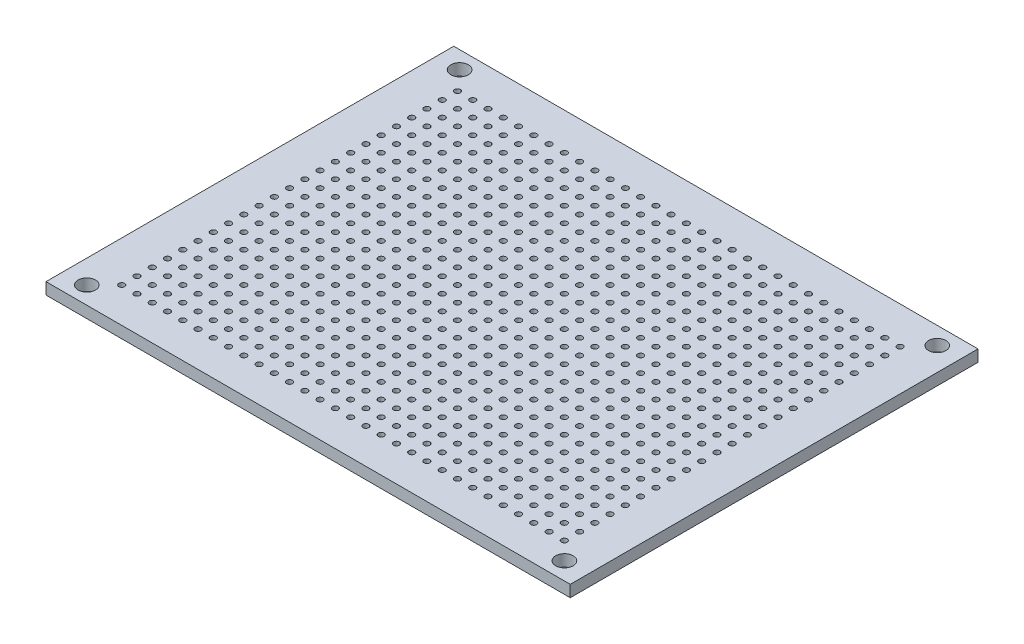
SolidWorks part; units mm, degrees
ref_plane "Front Plane" through (0, 0, 0) normal (0, 0, 1) x (1, 0, 0)
ref_plane "Top Plane" through (0, 0, 0) normal (0, 1, 0) x (1, 0, 0)
ref_plane "Right Plane" through (0, 0, 0) normal (1, 0, 0) x (0, 0, -1)
sketch "Sketch1" plane through (0, 0, 0) normal (0, 1, 0) x (1, 0, 0)
  line L0 (0, -44.7135) -> (0, 42.4067) construction
  line L1 (-45, 35) -> (45, 35)
  line L2 (-45, 35) -> (-45, -35)
  line L3 (-45, -35) -> (45, -35)
  line L4 (45, 35) -> (45, -35)
  line L5 (-45, 35) -> (45, -35) construction
  line L6 (-45, -35) -> (45, 35) construction
  line L7 (-54.5641, 0) -> (59.3866, 0) construction
  circle A0 centre (-41, -32) radius 1.5
  circle A1 centre (-38, -29) radius 0.5
  circle A2 centre (-35.38, -29) radius 0.5
  circle A3 centre (-32.76, -29) radius 0.5
  circle A4 centre (-30.14, -29) radius 0.5
  circle A5 centre (-27.52, -29) radius 0.5
  circle A6 centre (-24.9, -29) radius 0.5
  circle A7 centre (-22.28, -29) radius 0.5
  circle A8 centre (-19.66, -29) radius 0.5
  circle A9 centre (-17.04, -29) radius 0.5
  circle A10 centre (-14.42, -29) radius 0.5
  circle A11 centre (-11.8, -29) radius 0.5
  circle A12 centre (-9.18, -29) radius 0.5
  circle A13 centre (-6.56, -29) radius 0.5
  circle A14 centre (-3.94, -29) radius 0.5
  circle A15 centre (-1.32, -29) radius 0.5
  circle A16 centre (1.3, -29) radius 0.5
  circle A17 centre (3.92, -29) radius 0.5
  circle A18 centre (6.54, -29) radius 0.5
  circle A19 centre (9.16, -29) radius 0.5
  circle A20 centre (11.78, -29) radius 0.5
  circle A21 centre (14.4, -29) radius 0.5
  circle A22 centre (17.02, -29) radius 0.5
  circle A23 centre (19.64, -29) radius 0.5
  circle A24 centre (22.26, -29) radius 0.5
  circle A25 centre (24.88, -29) radius 0.5
  circle A26 centre (27.5, -29) radius 0.5
  circle A27 centre (30.12, -29) radius 0.5
  circle A28 centre (32.74, -29) radius 0.5
  circle A29 centre (35.36, -29) radius 0.5
  circle A30 centre (37.98, -29) radius 0.5
  circle A31 centre (-38, -26.38) radius 0.5
  circle A32 centre (-35.38, -26.38) radius 0.5
  circle A33 centre (-32.76, -26.38) radius 0.5
  circle A34 centre (-30.14, -26.38) radius 0.5
  circle A35 centre (-27.52, -26.38) radius 0.5
  circle A36 centre (-24.9, -26.38) radius 0.5
  circle A37 centre (-22.28, -26.38) radius 0.5
  circle A38 centre (-19.66, -26.38) radius 0.5
  circle A39 centre (-17.04, -26.38) radius 0.5
  circle A40 centre (-14.42, -26.38) radius 0.5
  circle A41 centre (-11.8, -26.38) radius 0.5
  circle A42 centre (-9.18, -26.38) radius 0.5
  circle A43 centre (-6.56, -26.38) radius 0.5
  circle A44 centre (-3.94, -26.38) radius 0.5
  circle A45 centre (-1.32, -26.38) radius 0.5
  circle A46 centre (1.3, -26.38) radius 0.5
  circle A47 centre (3.92, -26.38) radius 0.5
  circle A48 centre (6.54, -26.38) radius 0.5
  circle A49 centre (9.16, -26.38) radius 0.5
  circle A50 centre (11.78, -26.38) radius 0.5
  circle A51 centre (14.4, -26.38) radius 0.5
  circle A52 centre (17.02, -26.38) radius 0.5
  circle A53 centre (19.64, -26.38) radius 0.5
  circle A54 centre (22.26, -26.38) radius 0.5
  circle A55 centre (24.88, -26.38) radius 0.5
  circle A56 centre (27.5, -26.38) radius 0.5
  circle A57 centre (30.12, -26.38) radius 0.5
  circle A58 centre (32.74, -26.38) radius 0.5
  circle A59 centre (35.36, -26.38) radius 0.5
  circle A60 centre (37.98, -26.38) radius 0.5
  circle A61 centre (-38, -23.76) radius 0.5
  circle A62 centre (-35.38, -23.76) radius 0.5
  circle A63 centre (-32.76, -23.76) radius 0.5
  circle A64 centre (-30.14, -23.76) radius 0.5
  circle A65 centre (-27.52, -23.76) radius 0.5
  circle A66 centre (-24.9, -23.76) radius 0.5
  circle A67 centre (-22.28, -23.76) radius 0.5
  circle A68 centre (-19.66, -23.76) radius 0.5
  circle A69 centre (-17.04, -23.76) radius 0.5
  circle A70 centre (-14.42, -23.76) radius 0.5
  circle A71 centre (-11.8, -23.76) radius 0.5
  circle A72 centre (-9.18, -23.76) radius 0.5
  circle A73 centre (-6.56, -23.76) radius 0.5
  circle A74 centre (-3.94, -23.76) radius 0.5
  circle A75 centre (-1.32, -23.76) radius 0.5
  circle A76 centre (1.3, -23.76) radius 0.5
  circle A77 centre (3.92, -23.76) radius 0.5
  circle A78 centre (6.54, -23.76) radius 0.5
  circle A79 centre (9.16, -23.76) radius 0.5
  circle A80 centre (11.78, -23.76) radius 0.5
  circle A81 centre (14.4, -23.76) radius 0.5
  circle A82 centre (17.02, -23.76) radius 0.5
  circle A83 centre (19.64, -23.76) radius 0.5
  circle A84 centre (22.26, -23.76) radius 0.5
  circle A85 centre (24.88, -23.76) radius 0.5
  circle A86 centre (27.5, -23.76) radius 0.5
  circle A87 centre (30.12, -23.76) radius 0.5
  circle A88 centre (32.74, -23.76) radius 0.5
  circle A89 centre (35.36, -23.76) radius 0.5
  circle A90 centre (37.98, -23.76) radius 0.5
  circle A91 centre (-38, -21.14) radius 0.5
  circle A92 centre (-35.38, -21.14) radius 0.5
  circle A93 centre (-32.76, -21.14) radius 0.5
  circle A94 centre (-30.14, -21.14) radius 0.5
  circle A95 centre (-27.52, -21.14) radius 0.5
  circle A96 centre (-24.9, -21.14) radius 0.5
  circle A97 centre (-22.28, -21.14) radius 0.5
  circle A98 centre (-19.66, -21.14) radius 0.5
  circle A99 centre (-17.04, -21.14) radius 0.5
  circle A100 centre (-14.42, -21.14) radius 0.5
  circle A101 centre (-11.8, -21.14) radius 0.5
  circle A102 centre (-9.18, -21.14) radius 0.5
  circle A103 centre (-6.56, -21.14) radius 0.5
  circle A104 centre (-3.94, -21.14) radius 0.5
  circle A105 centre (-1.32, -21.14) radius 0.5
  circle A106 centre (1.3, -21.14) radius 0.5
  circle A107 centre (3.92, -21.14) radius 0.5
  circle A108 centre (6.54, -21.14) radius 0.5
  circle A109 centre (9.16, -21.14) radius 0.5
  circle A110 centre (11.78, -21.14) radius 0.5
  circle A111 centre (14.4, -21.14) radius 0.5
  circle A112 centre (17.02, -21.14) radius 0.5
  circle A113 centre (19.64, -21.14) radius 0.5
  circle A114 centre (22.26, -21.14) radius 0.5
  circle A115 centre (24.88, -21.14) radius 0.5
  circle A116 centre (27.5, -21.14) radius 0.5
  circle A117 centre (30.12, -21.14) radius 0.5
  circle A118 centre (32.74, -21.14) radius 0.5
  circle A119 centre (35.36, -21.14) radius 0.5
  circle A120 centre (37.98, -21.14) radius 0.5
  circle A121 centre (-38, -18.52) radius 0.5
  circle A122 centre (-35.38, -18.52) radius 0.5
  circle A123 centre (-32.76, -18.52) radius 0.5
  circle A124 centre (-30.14, -18.52) radius 0.5
  circle A125 centre (-27.52, -18.52) radius 0.5
  circle A126 centre (-24.9, -18.52) radius 0.5
  circle A127 centre (-22.28, -18.52) radius 0.5
  circle A128 centre (-19.66, -18.52) radius 0.5
  circle A129 centre (-17.04, -18.52) radius 0.5
  circle A130 centre (-14.42, -18.52) radius 0.5
  circle A131 centre (-11.8, -18.52) radius 0.5
  circle A132 centre (-9.18, -18.52) radius 0.5
  circle A133 centre (-6.56, -18.52) radius 0.5
  circle A134 centre (-3.94, -18.52) radius 0.5
  circle A135 centre (-1.32, -18.52) radius 0.5
  circle A136 centre (1.3, -18.52) radius 0.5
  circle A137 centre (3.92, -18.52) radius 0.5
  circle A138 centre (6.54, -18.52) radius 0.5
  circle A139 centre (9.16, -18.52) radius 0.5
  circle A140 centre (11.78, -18.52) radius 0.5
  circle A141 centre (14.4, -18.52) radius 0.5
  circle A142 centre (17.02, -18.52) radius 0.5
  circle A143 centre (19.64, -18.52) radius 0.5
  circle A144 centre (22.26, -18.52) radius 0.5
  circle A145 centre (24.88, -18.52) radius 0.5
  circle A146 centre (27.5, -18.52) radius 0.5
  circle A147 centre (30.12, -18.52) radius 0.5
  circle A148 centre (32.74, -18.52) radius 0.5
  circle A149 centre (35.36, -18.52) radius 0.5
  circle A150 centre (37.98, -18.52) radius 0.5
  circle A151 centre (-38, -15.9) radius 0.5
  circle A152 centre (-35.38, -15.9) radius 0.5
  circle A153 centre (-32.76, -15.9) radius 0.5
  circle A154 centre (-30.14, -15.9) radius 0.5
  circle A155 centre (-27.52, -15.9) radius 0.5
  circle A156 centre (-24.9, -15.9) radius 0.5
  circle A157 centre (-22.28, -15.9) radius 0.5
  circle A158 centre (-19.66, -15.9) radius 0.5
  circle A159 centre (-17.04, -15.9) radius 0.5
  circle A160 centre (-14.42, -15.9) radius 0.5
  circle A161 centre (-11.8, -15.9) radius 0.5
  circle A162 centre (-9.18, -15.9) radius 0.5
  circle A163 centre (-6.56, -15.9) radius 0.5
  circle A164 centre (-3.94, -15.9) radius 0.5
  circle A165 centre (-1.32, -15.9) radius 0.5
  circle A166 centre (1.3, -15.9) radius 0.5
  circle A167 centre (3.92, -15.9) radius 0.5
  circle A168 centre (6.54, -15.9) radius 0.5
  circle A169 centre (9.16, -15.9) radius 0.5
  circle A170 centre (11.78, -15.9) radius 0.5
  circle A171 centre (14.4, -15.9) radius 0.5
  circle A172 centre (17.02, -15.9) radius 0.5
  circle A173 centre (19.64, -15.9) radius 0.5
  circle A174 centre (22.26, -15.9) radius 0.5
  circle A175 centre (24.88, -15.9) radius 0.5
  circle A176 centre (27.5, -15.9) radius 0.5
  circle A177 centre (30.12, -15.9) radius 0.5
  circle A178 centre (32.74, -15.9) radius 0.5
  circle A179 centre (35.36, -15.9) radius 0.5
  circle A180 centre (37.98, -15.9) radius 0.5
  circle A181 centre (-38, -13.28) radius 0.5
  circle A182 centre (-35.38, -13.28) radius 0.5
  circle A183 centre (-32.76, -13.28) radius 0.5
  circle A184 centre (-30.14, -13.28) radius 0.5
  circle A185 centre (-27.52, -13.28) radius 0.5
  circle A186 centre (-24.9, -13.28) radius 0.5
  circle A187 centre (-22.28, -13.28) radius 0.5
  circle A188 centre (-19.66, -13.28) radius 0.5
  circle A189 centre (-17.04, -13.28) radius 0.5
  circle A190 centre (-14.42, -13.28) radius 0.5
  circle A191 centre (-11.8, -13.28) radius 0.5
  circle A192 centre (-9.18, -13.28) radius 0.5
  circle A193 centre (-6.56, -13.28) radius 0.5
  circle A194 centre (-3.94, -13.28) radius 0.5
  circle A195 centre (-1.32, -13.28) radius 0.5
  circle A196 centre (1.3, -13.28) radius 0.5
  circle A197 centre (3.92, -13.28) radius 0.5
  circle A198 centre (6.54, -13.28) radius 0.5
  circle A199 centre (9.16, -13.28) radius 0.5
  circle A200 centre (11.78, -13.28) radius 0.5
  circle A201 centre (14.4, -13.28) radius 0.5
  circle A202 centre (17.02, -13.28) radius 0.5
  circle A203 centre (19.64, -13.28) radius 0.5
  circle A204 centre (22.26, -13.28) radius 0.5
  circle A205 centre (24.88, -13.28) radius 0.5
  circle A206 centre (27.5, -13.28) radius 0.5
  circle A207 centre (30.12, -13.28) radius 0.5
  circle A208 centre (32.74, -13.28) radius 0.5
  circle A209 centre (35.36, -13.28) radius 0.5
  circle A210 centre (37.98, -13.28) radius 0.5
  circle A211 centre (-38, -10.66) radius 0.5
  circle A212 centre (-35.38, -10.66) radius 0.5
  circle A213 centre (-32.76, -10.66) radius 0.5
  circle A214 centre (-30.14, -10.66) radius 0.5
  circle A215 centre (-27.52, -10.66) radius 0.5
  circle A216 centre (-24.9, -10.66) radius 0.5
  circle A217 centre (-22.28, -10.66) radius 0.5
  circle A218 centre (-19.66, -10.66) radius 0.5
  circle A219 centre (-17.04, -10.66) radius 0.5
  circle A220 centre (-14.42, -10.66) radius 0.5
  circle A221 centre (-11.8, -10.66) radius 0.5
  circle A222 centre (-9.18, -10.66) radius 0.5
  circle A223 centre (-6.56, -10.66) radius 0.5
  circle A224 centre (-3.94, -10.66) radius 0.5
  circle A225 centre (-1.32, -10.66) radius 0.5
  circle A226 centre (1.3, -10.66) radius 0.5
  circle A227 centre (3.92, -10.66) radius 0.5
  circle A228 centre (6.54, -10.66) radius 0.5
  circle A229 centre (9.16, -10.66) radius 0.5
  circle A230 centre (11.78, -10.66) radius 0.5
  circle A231 centre (14.4, -10.66) radius 0.5
  circle A232 centre (17.02, -10.66) radius 0.5
  circle A233 centre (19.64, -10.66) radius 0.5
  circle A234 centre (22.26, -10.66) radius 0.5
  circle A235 centre (24.88, -10.66) radius 0.5
  circle A236 centre (27.5, -10.66) radius 0.5
  circle A237 centre (30.12, -10.66) radius 0.5
  circle A238 centre (32.74, -10.66) radius 0.5
  circle A239 centre (35.36, -10.66) radius 0.5
  circle A240 centre (37.98, -10.66) radius 0.5
  circle A241 centre (-38, -8.04) radius 0.5
  circle A242 centre (-35.38, -8.04) radius 0.5
  circle A243 centre (-32.76, -8.04) radius 0.5
  circle A244 centre (-30.14, -8.04) radius 0.5
  circle A245 centre (-27.52, -8.04) radius 0.5
  circle A246 centre (-24.9, -8.04) radius 0.5
  circle A247 centre (-22.28, -8.04) radius 0.5
  circle A248 centre (-19.66, -8.04) radius 0.5
  circle A249 centre (-17.04, -8.04) radius 0.5
  circle A250 centre (-14.42, -8.04) radius 0.5
  circle A251 centre (-11.8, -8.04) radius 0.5
  circle A252 centre (-9.18, -8.04) radius 0.5
  circle A253 centre (-6.56, -8.04) radius 0.5
  circle A254 centre (-3.94, -8.04) radius 0.5
  circle A255 centre (-1.32, -8.04) radius 0.5
  circle A256 centre (1.3, -8.04) radius 0.5
  circle A257 centre (3.92, -8.04) radius 0.5
  circle A258 centre (6.54, -8.04) radius 0.5
  circle A259 centre (9.16, -8.04) radius 0.5
  circle A260 centre (11.78, -8.04) radius 0.5
  circle A261 centre (14.4, -8.04) radius 0.5
  circle A262 centre (17.02, -8.04) radius 0.5
  circle A263 centre (19.64, -8.04) radius 0.5
  circle A264 centre (22.26, -8.04) radius 0.5
  circle A265 centre (24.88, -8.04) radius 0.5
  circle A266 centre (27.5, -8.04) radius 0.5
  circle A267 centre (30.12, -8.04) radius 0.5
  circle A268 centre (32.74, -8.04) radius 0.5
  circle A269 centre (35.36, -8.04) radius 0.5
  circle A270 centre (37.98, -8.04) radius 0.5
  circle A271 centre (-38, -5.42) radius 0.5
  circle A272 centre (-35.38, -5.42) radius 0.5
  circle A273 centre (-32.76, -5.42) radius 0.5
  circle A274 centre (-30.14, -5.42) radius 0.5
  circle A275 centre (-27.52, -5.42) radius 0.5
  circle A276 centre (-24.9, -5.42) radius 0.5
  circle A277 centre (-22.28, -5.42) radius 0.5
  circle A278 centre (-19.66, -5.42) radius 0.5
  circle A279 centre (-17.04, -5.42) radius 0.5
  circle A280 centre (-14.42, -5.42) radius 0.5
  circle A281 centre (-11.8, -5.42) radius 0.5
  circle A282 centre (-9.18, -5.42) radius 0.5
  circle A283 centre (-6.56, -5.42) radius 0.5
  circle A284 centre (-3.94, -5.42) radius 0.5
  circle A285 centre (-1.32, -5.42) radius 0.5
  circle A286 centre (1.3, -5.42) radius 0.5
  circle A287 centre (3.92, -5.42) radius 0.5
  circle A288 centre (6.54, -5.42) radius 0.5
  circle A289 centre (9.16, -5.42) radius 0.5
  circle A290 centre (11.78, -5.42) radius 0.5
  circle A291 centre (14.4, -5.42) radius 0.5
  circle A292 centre (17.02, -5.42) radius 0.5
  circle A293 centre (19.64, -5.42) radius 0.5
  circle A294 centre (22.26, -5.42) radius 0.5
  circle A295 centre (24.88, -5.42) radius 0.5
  circle A296 centre (27.5, -5.42) radius 0.5
  circle A297 centre (30.12, -5.42) radius 0.5
  circle A298 centre (32.74, -5.42) radius 0.5
  circle A299 centre (35.36, -5.42) radius 0.5
  circle A300 centre (37.98, -5.42) radius 0.5
  circle A301 centre (-38, -2.8) radius 0.5
  circle A302 centre (-35.38, -2.8) radius 0.5
  circle A303 centre (-32.76, -2.8) radius 0.5
  circle A304 centre (-30.14, -2.8) radius 0.5
  circle A305 centre (-27.52, -2.8) radius 0.5
  circle A306 centre (-24.9, -2.8) radius 0.5
  circle A307 centre (-22.28, -2.8) radius 0.5
  circle A308 centre (-19.66, -2.8) radius 0.5
  circle A309 centre (-17.04, -2.8) radius 0.5
  circle A310 centre (-14.42, -2.8) radius 0.5
  circle A311 centre (-11.8, -2.8) radius 0.5
  circle A312 centre (-9.18, -2.8) radius 0.5
  circle A313 centre (-6.56, -2.8) radius 0.5
  circle A314 centre (-3.94, -2.8) radius 0.5
  circle A315 centre (-1.32, -2.8) radius 0.5
  circle A316 centre (1.3, -2.8) radius 0.5
  circle A317 centre (3.92, -2.8) radius 0.5
  circle A318 centre (6.54, -2.8) radius 0.5
  circle A319 centre (9.16, -2.8) radius 0.5
  circle A320 centre (11.78, -2.8) radius 0.5
  circle A321 centre (14.4, -2.8) radius 0.5
  circle A322 centre (17.02, -2.8) radius 0.5
  circle A323 centre (19.64, -2.8) radius 0.5
  circle A324 centre (22.26, -2.8) radius 0.5
  circle A325 centre (24.88, -2.8) radius 0.5
  circle A326 centre (27.5, -2.8) radius 0.5
  circle A327 centre (30.12, -2.8) radius 0.5
  circle A328 centre (32.74, -2.8) radius 0.5
  circle A329 centre (35.36, -2.8) radius 0.5
  circle A330 centre (37.98, -2.8) radius 0.5
  circle A331 centre (-38, -0.18) radius 0.5
  circle A332 centre (-35.38, -0.18) radius 0.5
  circle A333 centre (-32.76, -0.18) radius 0.5
  circle A334 centre (-30.14, -0.18) radius 0.5
  circle A335 centre (-27.52, -0.18) radius 0.5
  circle A336 centre (-24.9, -0.18) radius 0.5
  circle A337 centre (-22.28, -0.18) radius 0.5
  circle A338 centre (-19.66, -0.18) radius 0.5
  circle A339 centre (-17.04, -0.18) radius 0.5
  circle A340 centre (-14.42, -0.18) radius 0.5
  circle A341 centre (-11.8, -0.18) radius 0.5
  circle A342 centre (-9.18, -0.18) radius 0.5
  circle A343 centre (-6.56, -0.18) radius 0.5
  circle A344 centre (-3.94, -0.18) radius 0.5
  circle A345 centre (-1.32, -0.18) radius 0.5
  circle A346 centre (1.3, -0.18) radius 0.5
  circle A347 centre (3.92, -0.18) radius 0.5
  circle A348 centre (6.54, -0.18) radius 0.5
  circle A349 centre (9.16, -0.18) radius 0.5
  circle A350 centre (11.78, -0.18) radius 0.5
  circle A351 centre (14.4, -0.18) radius 0.5
  circle A352 centre (17.02, -0.18) radius 0.5
  circle A353 centre (19.64, -0.18) radius 0.5
  circle A354 centre (22.26, -0.18) radius 0.5
  circle A355 centre (24.88, -0.18) radius 0.5
  circle A356 centre (27.5, -0.18) radius 0.5
  circle A357 centre (30.12, -0.18) radius 0.5
  circle A358 centre (32.74, -0.18) radius 0.5
  circle A359 centre (35.36, -0.18) radius 0.5
  circle A360 centre (37.98, -0.18) radius 0.5
  circle A361 centre (-38, 2.44) radius 0.5
  circle A362 centre (-35.38, 2.44) radius 0.5
  circle A363 centre (-32.76, 2.44) radius 0.5
  circle A364 centre (-30.14, 2.44) radius 0.5
  circle A365 centre (-27.52, 2.44) radius 0.5
  circle A366 centre (-24.9, 2.44) radius 0.5
  circle A367 centre (-22.28, 2.44) radius 0.5
  circle A368 centre (-19.66, 2.44) radius 0.5
  circle A369 centre (-17.04, 2.44) radius 0.5
  circle A370 centre (-14.42, 2.44) radius 0.5
  circle A371 centre (-11.8, 2.44) radius 0.5
  circle A372 centre (-9.18, 2.44) radius 0.5
  circle A373 centre (-6.56, 2.44) radius 0.5
  circle A374 centre (-3.94, 2.44) radius 0.5
  circle A375 centre (-1.32, 2.44) radius 0.5
  circle A376 centre (1.3, 2.44) radius 0.5
  circle A377 centre (3.92, 2.44) radius 0.5
  circle A378 centre (6.54, 2.44) radius 0.5
  circle A379 centre (9.16, 2.44) radius 0.5
  circle A380 centre (11.78, 2.44) radius 0.5
  circle A381 centre (14.4, 2.44) radius 0.5
  circle A382 centre (17.02, 2.44) radius 0.5
  circle A383 centre (19.64, 2.44) radius 0.5
  circle A384 centre (22.26, 2.44) radius 0.5
  circle A385 centre (24.88, 2.44) radius 0.5
  circle A386 centre (27.5, 2.44) radius 0.5
  circle A387 centre (30.12, 2.44) radius 0.5
  circle A388 centre (32.74, 2.44) radius 0.5
  circle A389 centre (35.36, 2.44) radius 0.5
  circle A390 centre (37.98, 2.44) radius 0.5
  circle A391 centre (-38, 5.06) radius 0.5
  circle A392 centre (-35.38, 5.06) radius 0.5
  circle A393 centre (-32.76, 5.06) radius 0.5
  circle A394 centre (-30.14, 5.06) radius 0.5
  circle A395 centre (-27.52, 5.06) radius 0.5
  circle A396 centre (-24.9, 5.06) radius 0.5
  circle A397 centre (-22.28, 5.06) radius 0.5
  circle A398 centre (-19.66, 5.06) radius 0.5
  circle A399 centre (-17.04, 5.06) radius 0.5
  circle A400 centre (-14.42, 5.06) radius 0.5
  circle A401 centre (-11.8, 5.06) radius 0.5
  circle A402 centre (-9.18, 5.06) radius 0.5
  circle A403 centre (-6.56, 5.06) radius 0.5
  circle A404 centre (-3.94, 5.06) radius 0.5
  circle A405 centre (-1.32, 5.06) radius 0.5
  circle A406 centre (1.3, 5.06) radius 0.5
  circle A407 centre (3.92, 5.06) radius 0.5
  circle A408 centre (6.54, 5.06) radius 0.5
  circle A409 centre (9.16, 5.06) radius 0.5
  circle A410 centre (11.78, 5.06) radius 0.5
  circle A411 centre (14.4, 5.06) radius 0.5
  circle A412 centre (17.02, 5.06) radius 0.5
  circle A413 centre (19.64, 5.06) radius 0.5
  circle A414 centre (22.26, 5.06) radius 0.5
  circle A415 centre (24.88, 5.06) radius 0.5
  circle A416 centre (27.5, 5.06) radius 0.5
  circle A417 centre (30.12, 5.06) radius 0.5
  circle A418 centre (32.74, 5.06) radius 0.5
  circle A419 centre (35.36, 5.06) radius 0.5
  circle A420 centre (37.98, 5.06) radius 0.5
  circle A421 centre (-38, 7.68) radius 0.5
  circle A422 centre (-35.38, 7.68) radius 0.5
  circle A423 centre (-32.76, 7.68) radius 0.5
  circle A424 centre (-30.14, 7.68) radius 0.5
  circle A425 centre (-27.52, 7.68) radius 0.5
  circle A426 centre (-24.9, 7.68) radius 0.5
  circle A427 centre (-22.28, 7.68) radius 0.5
  circle A428 centre (-19.66, 7.68) radius 0.5
  circle A429 centre (-17.04, 7.68) radius 0.5
  circle A430 centre (-14.42, 7.68) radius 0.5
  circle A431 centre (-11.8, 7.68) radius 0.5
  circle A432 centre (-9.18, 7.68) radius 0.5
  circle A433 centre (-6.56, 7.68) radius 0.5
  circle A434 centre (-3.94, 7.68) radius 0.5
  circle A435 centre (-1.32, 7.68) radius 0.5
  circle A436 centre (1.3, 7.68) radius 0.5
  circle A437 centre (3.92, 7.68) radius 0.5
  circle A438 centre (6.54, 7.68) radius 0.5
  circle A439 centre (9.16, 7.68) radius 0.5
  circle A440 centre (11.78, 7.68) radius 0.5
  circle A441 centre (14.4, 7.68) radius 0.5
  circle A442 centre (17.02, 7.68) radius 0.5
  circle A443 centre (19.64, 7.68) radius 0.5
  circle A444 centre (22.26, 7.68) radius 0.5
  circle A445 centre (24.88, 7.68) radius 0.5
  circle A446 centre (27.5, 7.68) radius 0.5
  circle A447 centre (30.12, 7.68) radius 0.5
  circle A448 centre (32.74, 7.68) radius 0.5
  circle A449 centre (35.36, 7.68) radius 0.5
  circle A450 centre (37.98, 7.68) radius 0.5
  circle A451 centre (-38, 10.3) radius 0.5
  circle A452 centre (-35.38, 10.3) radius 0.5
  circle A453 centre (-32.76, 10.3) radius 0.5
  circle A454 centre (-30.14, 10.3) radius 0.5
  circle A455 centre (-27.52, 10.3) radius 0.5
  circle A456 centre (-24.9, 10.3) radius 0.5
  circle A457 centre (-22.28, 10.3) radius 0.5
  circle A458 centre (-19.66, 10.3) radius 0.5
  circle A459 centre (-17.04, 10.3) radius 0.5
  circle A460 centre (-14.42, 10.3) radius 0.5
  circle A461 centre (-11.8, 10.3) radius 0.5
  circle A462 centre (-9.18, 10.3) radius 0.5
  circle A463 centre (-6.56, 10.3) radius 0.5
  circle A464 centre (-3.94, 10.3) radius 0.5
  circle A465 centre (-1.32, 10.3) radius 0.5
  circle A466 centre (1.3, 10.3) radius 0.5
  circle A467 centre (3.92, 10.3) radius 0.5
  circle A468 centre (6.54, 10.3) radius 0.5
  circle A469 centre (9.16, 10.3) radius 0.5
  circle A470 centre (11.78, 10.3) radius 0.5
  circle A471 centre (14.4, 10.3) radius 0.5
  circle A472 centre (17.02, 10.3) radius 0.5
  circle A473 centre (19.64, 10.3) radius 0.5
  circle A474 centre (22.26, 10.3) radius 0.5
  circle A475 centre (24.88, 10.3) radius 0.5
  circle A476 centre (27.5, 10.3) radius 0.5
  circle A477 centre (30.12, 10.3) radius 0.5
  circle A478 centre (32.74, 10.3) radius 0.5
  circle A479 centre (35.36, 10.3) radius 0.5
  circle A480 centre (37.98, 10.3) radius 0.5
  circle A481 centre (-38, 12.92) radius 0.5
  circle A482 centre (-35.38, 12.92) radius 0.5
  circle A483 centre (-32.76, 12.92) radius 0.5
  circle A484 centre (-30.14, 12.92) radius 0.5
  circle A485 centre (-27.52, 12.92) radius 0.5
  circle A486 centre (-24.9, 12.92) radius 0.5
  circle A487 centre (-22.28, 12.92) radius 0.5
  circle A488 centre (-19.66, 12.92) radius 0.5
  circle A489 centre (-17.04, 12.92) radius 0.5
  circle A490 centre (-14.42, 12.92) radius 0.5
  circle A491 centre (-11.8, 12.92) radius 0.5
  circle A492 centre (-9.18, 12.92) radius 0.5
  circle A493 centre (-6.56, 12.92) radius 0.5
  circle A494 centre (-3.94, 12.92) radius 0.5
  circle A495 centre (-1.32, 12.92) radius 0.5
  circle A496 centre (1.3, 12.92) radius 0.5
  circle A497 centre (3.92, 12.92) radius 0.5
  circle A498 centre (6.54, 12.92) radius 0.5
  circle A499 centre (9.16, 12.92) radius 0.5
  circle A500 centre (11.78, 12.92) radius 0.5
  circle A501 centre (14.4, 12.92) radius 0.5
  circle A502 centre (17.02, 12.92) radius 0.5
  circle A503 centre (19.64, 12.92) radius 0.5
  circle A504 centre (22.26, 12.92) radius 0.5
  circle A505 centre (24.88, 12.92) radius 0.5
  circle A506 centre (27.5, 12.92) radius 0.5
  circle A507 centre (30.12, 12.92) radius 0.5
  circle A508 centre (32.74, 12.92) radius 0.5
  circle A509 centre (35.36, 12.92) radius 0.5
  circle A510 centre (37.98, 12.92) radius 0.5
  circle A511 centre (-38, 15.54) radius 0.5
  circle A512 centre (-35.38, 15.54) radius 0.5
  circle A513 centre (-32.76, 15.54) radius 0.5
  circle A514 centre (-30.14, 15.54) radius 0.5
  circle A515 centre (-27.52, 15.54) radius 0.5
  circle A516 centre (-24.9, 15.54) radius 0.5
  circle A517 centre (-22.28, 15.54) radius 0.5
  circle A518 centre (-19.66, 15.54) radius 0.5
  circle A519 centre (-17.04, 15.54) radius 0.5
  circle A520 centre (-14.42, 15.54) radius 0.5
  circle A521 centre (-11.8, 15.54) radius 0.5
  circle A522 centre (-9.18, 15.54) radius 0.5
  circle A523 centre (-6.56, 15.54) radius 0.5
  circle A524 centre (-3.94, 15.54) radius 0.5
  circle A525 centre (-1.32, 15.54) radius 0.5
  circle A526 centre (1.3, 15.54) radius 0.5
  circle A527 centre (3.92, 15.54) radius 0.5
  circle A528 centre (6.54, 15.54) radius 0.5
  circle A529 centre (9.16, 15.54) radius 0.5
  circle A530 centre (11.78, 15.54) radius 0.5
  circle A531 centre (14.4, 15.54) radius 0.5
  circle A532 centre (17.02, 15.54) radius 0.5
  circle A533 centre (19.64, 15.54) radius 0.5
  circle A534 centre (22.26, 15.54) radius 0.5
  circle A535 centre (24.88, 15.54) radius 0.5
  circle A536 centre (27.5, 15.54) radius 0.5
  circle A537 centre (30.12, 15.54) radius 0.5
  circle A538 centre (32.74, 15.54) radius 0.5
  circle A539 centre (35.36, 15.54) radius 0.5
  circle A540 centre (37.98, 15.54) radius 0.5
  circle A541 centre (-38, 18.16) radius 0.5
  circle A542 centre (-35.38, 18.16) radius 0.5
  circle A543 centre (-32.76, 18.16) radius 0.5
  circle A544 centre (-30.14, 18.16) radius 0.5
  circle A545 centre (-27.52, 18.16) radius 0.5
  circle A546 centre (-24.9, 18.16) radius 0.5
  circle A547 centre (-22.28, 18.16) radius 0.5
  circle A548 centre (-19.66, 18.16) radius 0.5
  circle A549 centre (-17.04, 18.16) radius 0.5
  circle A550 centre (-14.42, 18.16) radius 0.5
  circle A551 centre (-11.8, 18.16) radius 0.5
  circle A552 centre (-9.18, 18.16) radius 0.5
  circle A553 centre (-6.56, 18.16) radius 0.5
  circle A554 centre (-3.94, 18.16) radius 0.5
  circle A555 centre (-1.32, 18.16) radius 0.5
  circle A556 centre (1.3, 18.16) radius 0.5
  circle A557 centre (3.92, 18.16) radius 0.5
  circle A558 centre (6.54, 18.16) radius 0.5
  circle A559 centre (9.16, 18.16) radius 0.5
  circle A560 centre (11.78, 18.16) radius 0.5
  circle A561 centre (14.4, 18.16) radius 0.5
  circle A562 centre (17.02, 18.16) radius 0.5
  circle A563 centre (19.64, 18.16) radius 0.5
  circle A564 centre (22.26, 18.16) radius 0.5
  circle A565 centre (24.88, 18.16) radius 0.5
  circle A566 centre (27.5, 18.16) radius 0.5
  circle A567 centre (30.12, 18.16) radius 0.5
  circle A568 centre (32.74, 18.16) radius 0.5
  circle A569 centre (35.36, 18.16) radius 0.5
  circle A570 centre (37.98, 18.16) radius 0.5
  circle A571 centre (-38, 20.78) radius 0.5
  circle A572 centre (-35.38, 20.78) radius 0.5
  circle A573 centre (-32.76, 20.78) radius 0.5
  circle A574 centre (-30.14, 20.78) radius 0.5
  circle A575 centre (-27.52, 20.78) radius 0.5
  circle A576 centre (-24.9, 20.78) radius 0.5
  circle A577 centre (-22.28, 20.78) radius 0.5
  circle A578 centre (-19.66, 20.78) radius 0.5
  circle A579 centre (-17.04, 20.78) radius 0.5
  circle A580 centre (-14.42, 20.78) radius 0.5
  circle A581 centre (-11.8, 20.78) radius 0.5
  circle A582 centre (-9.18, 20.78) radius 0.5
  circle A583 centre (-6.56, 20.78) radius 0.5
  circle A584 centre (-3.94, 20.78) radius 0.5
  circle A585 centre (-1.32, 20.78) radius 0.5
  circle A586 centre (1.3, 20.78) radius 0.5
  circle A587 centre (3.92, 20.78) radius 0.5
  circle A588 centre (6.54, 20.78) radius 0.5
  circle A589 centre (9.16, 20.78) radius 0.5
  circle A590 centre (11.78, 20.78) radius 0.5
  circle A591 centre (14.4, 20.78) radius 0.5
  circle A592 centre (17.02, 20.78) radius 0.5
  circle A593 centre (19.64, 20.78) radius 0.5
  circle A594 centre (22.26, 20.78) radius 0.5
  circle A595 centre (24.88, 20.78) radius 0.5
  circle A596 centre (27.5, 20.78) radius 0.5
  circle A597 centre (30.12, 20.78) radius 0.5
  circle A598 centre (32.74, 20.78) radius 0.5
  circle A599 centre (35.36, 20.78) radius 0.5
  circle A600 centre (37.98, 20.78) radius 0.5
  circle A601 centre (-38, 23.4) radius 0.5
  circle A602 centre (-35.38, 23.4) radius 0.5
  circle A603 centre (-32.76, 23.4) radius 0.5
  circle A604 centre (-30.14, 23.4) radius 0.5
  circle A605 centre (-27.52, 23.4) radius 0.5
  circle A606 centre (-24.9, 23.4) radius 0.5
  circle A607 centre (-22.28, 23.4) radius 0.5
  circle A608 centre (-19.66, 23.4) radius 0.5
  circle A609 centre (-17.04, 23.4) radius 0.5
  circle A610 centre (-14.42, 23.4) radius 0.5
  circle A611 centre (-11.8, 23.4) radius 0.5
  circle A612 centre (-9.18, 23.4) radius 0.5
  circle A613 centre (-6.56, 23.4) radius 0.5
  circle A614 centre (-3.94, 23.4) radius 0.5
  circle A615 centre (-1.32, 23.4) radius 0.5
  circle A616 centre (1.3, 23.4) radius 0.5
  circle A617 centre (3.92, 23.4) radius 0.5
  circle A618 centre (6.54, 23.4) radius 0.5
  circle A619 centre (9.16, 23.4) radius 0.5
  circle A620 centre (11.78, 23.4) radius 0.5
  circle A621 centre (14.4, 23.4) radius 0.5
  circle A622 centre (17.02, 23.4) radius 0.5
  circle A623 centre (19.64, 23.4) radius 0.5
  circle A624 centre (22.26, 23.4) radius 0.5
  circle A625 centre (24.88, 23.4) radius 0.5
  circle A626 centre (27.5, 23.4) radius 0.5
  circle A627 centre (30.12, 23.4) radius 0.5
  circle A628 centre (32.74, 23.4) radius 0.5
  circle A629 centre (35.36, 23.4) radius 0.5
  circle A630 centre (37.98, 23.4) radius 0.5
  circle A631 centre (-38, 26.02) radius 0.5
  circle A632 centre (-35.38, 26.02) radius 0.5
  circle A633 centre (-32.76, 26.02) radius 0.5
  circle A634 centre (-30.14, 26.02) radius 0.5
  circle A635 centre (-27.52, 26.02) radius 0.5
  circle A636 centre (-24.9, 26.02) radius 0.5
  circle A637 centre (-22.28, 26.02) radius 0.5
  circle A638 centre (-19.66, 26.02) radius 0.5
  circle A639 centre (-17.04, 26.02) radius 0.5
  circle A640 centre (-14.42, 26.02) radius 0.5
  circle A641 centre (-11.8, 26.02) radius 0.5
  circle A642 centre (-9.18, 26.02) radius 0.5
  circle A643 centre (-6.56, 26.02) radius 0.5
  circle A644 centre (-3.94, 26.02) radius 0.5
  circle A645 centre (-1.32, 26.02) radius 0.5
  circle A646 centre (1.3, 26.02) radius 0.5
  circle A647 centre (3.92, 26.02) radius 0.5
  circle A648 centre (6.54, 26.02) radius 0.5
  circle A649 centre (9.16, 26.02) radius 0.5
  circle A650 centre (11.78, 26.02) radius 0.5
  circle A651 centre (14.4, 26.02) radius 0.5
  circle A652 centre (17.02, 26.02) radius 0.5
  circle A653 centre (19.64, 26.02) radius 0.5
  circle A654 centre (22.26, 26.02) radius 0.5
  circle A655 centre (24.88, 26.02) radius 0.5
  circle A656 centre (27.5, 26.02) radius 0.5
  circle A657 centre (30.12, 26.02) radius 0.5
  circle A658 centre (32.74, 26.02) radius 0.5
  circle A659 centre (35.36, 26.02) radius 0.5
  circle A660 centre (37.98, 26.02) radius 0.5
  circle A661 centre (-38, 28.64) radius 0.5
  circle A662 centre (-35.38, 28.64) radius 0.5
  circle A663 centre (-32.76, 28.64) radius 0.5
  circle A664 centre (-30.14, 28.64) radius 0.5
  circle A665 centre (-27.52, 28.64) radius 0.5
  circle A666 centre (-24.9, 28.64) radius 0.5
  circle A667 centre (-22.28, 28.64) radius 0.5
  circle A668 centre (-19.66, 28.64) radius 0.5
  circle A669 centre (-17.04, 28.64) radius 0.5
  circle A670 centre (-14.42, 28.64) radius 0.5
  circle A671 centre (-11.8, 28.64) radius 0.5
  circle A672 centre (-9.18, 28.64) radius 0.5
  circle A673 centre (-6.56, 28.64) radius 0.5
  circle A674 centre (-3.94, 28.64) radius 0.5
  circle A675 centre (-1.32, 28.64) radius 0.5
  circle A676 centre (1.3, 28.64) radius 0.5
  circle A677 centre (3.92, 28.64) radius 0.5
  circle A678 centre (6.54, 28.64) radius 0.5
  circle A679 centre (9.16, 28.64) radius 0.5
  circle A680 centre (11.78, 28.64) radius 0.5
  circle A681 centre (14.4, 28.64) radius 0.5
  circle A682 centre (17.02, 28.64) radius 0.5
  circle A683 centre (19.64, 28.64) radius 0.5
  circle A684 centre (22.26, 28.64) radius 0.5
  circle A685 centre (24.88, 28.64) radius 0.5
  circle A686 centre (27.5, 28.64) radius 0.5
  circle A687 centre (30.12, 28.64) radius 0.5
  circle A688 centre (32.74, 28.64) radius 0.5
  circle A689 centre (35.36, 28.64) radius 0.5
  circle A690 centre (37.98, 28.64) radius 0.5
  circle A691 centre (41, -32) radius 1.5
  circle A692 centre (-41, 32) radius 1.5
  circle A693 centre (41, 32) radius 1.5
  point P0 (0, 0)
  dimension "D5" = 3
  dimension "D8" = 1
  dimension "D1" = 90
  dimension "D2" = 70
  dimension "D3" = 3
  dimension "D4" = 4
  dimension "D6" = 6
  dimension "D7" = 7
  dimension "D10" = 2.62
  dimension "D9" = 30
  dimension "D11" = 23
extrude "Boss-Extrude1" add sketch "Sketch1" along normal blind 2
